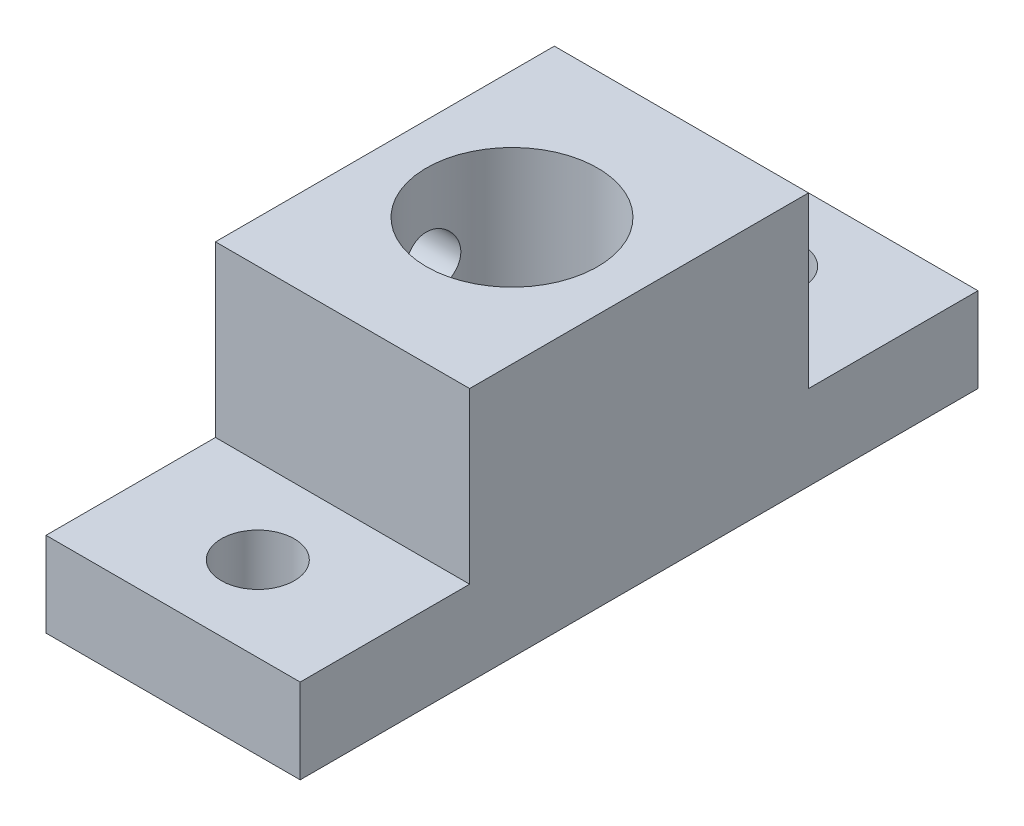
SolidWorks part; units mm, degrees
ref_plane "Front Plane" through (0, 0, 0) normal (0, 0, 1) x (1, 0, 0)
ref_plane "Top Plane" through (0, 0, 0) normal (0, 1, 0) x (1, 0, 0)
ref_plane "Right Plane" through (0, 0, 0) normal (1, 0, 0) x (0, 0, -1)
sketch "Sketch1" plane through (0, 0, 0) normal (1, 0, 0) x (0, 0, -1)
  line L0 (-10, -10) -> (-10, 0)
  line L1 (-10, 0) -> (10, 0)
  line L2 (10, 0) -> (10, -10)
  line L3 (10, -10) -> (20, -10)
  line L4 (20, -10) -> (20, -15)
  line L5 (20, -15) -> (-20, -15)
  line L6 (-20, -15) -> (-20, -10)
  line L7 (-20, -10) -> (-10, -10)
  point P2 (0, 0)
  dimension "D1" = 40
  dimension "D2" = 20
  dimension "D3" = 5
  dimension "D4" = 10
extrude "Boss-Extrude1" add sketch "Sketch1" along normal mid plane 15
sketch "Sketch2" plane through (0, 0, 0) normal (0, 1, 0) x (1, 0, 0)
  circle A0 centre (0, 0) radius 5.05
  dimension "D1" = 10.1
extrude "Cut-Extrude1" cut sketch "Sketch2" against normal blind 10
hole_wizard "#8-32 Tapped Hole1" positions "Sketch3" profile "Sketch4" tap size "#8-32" standard "ANSI Inch" end condition up to next
sketch "Sketch3" plane through (-7.5, 0, 0) normal (-1, 0, 0) x (0, 0, 1)
  line L0 (0, -5) -> (0, 0) construction
  point P0 (0, -5)
  dimension "D1" = 5
cosmetic thread "Hole Thread1" parameters "D2"=4.1656
sketch "Sketch4" plane through (-7.5, -5, 0) normal (0, 1, 0) x (0, 0, 1)
  line L0 (0, 0) -> (0, 2.45)
  line L1 (0, 2.45) -> (1.7272, 2.45)
  line L2 (1.7272, 2.45) -> (1.7272, 0)
  line L5 (1.7272, 0) -> (0, 0)
  line L11 (0, -6.35) -> (0, 107.95) construction
  dimension "Thru Tap Drill Dia." = 3.4544
  dimension "Thru Tap Drill Depth" = 2.45
sketch "Sketch5" plane through (0, -10, 0) normal (0, 1, 0) x (1, 0, 0)
  line L0 (0, 15) -> (0, -15) construction
  line L1 (0, 15) -> (-7.5, 15) construction
  line L2 (-7.5, 20) -> (-7.5, 10) construction
  circle A0 centre (0, 15) radius 2.15
  circle A1 centre (0, -15) radius 2.15
  point P4 (0, 0)
  dimension "D1" = 4.3
extrude "Cut-Extrude2" cut sketch "Sketch5" against normal through all
